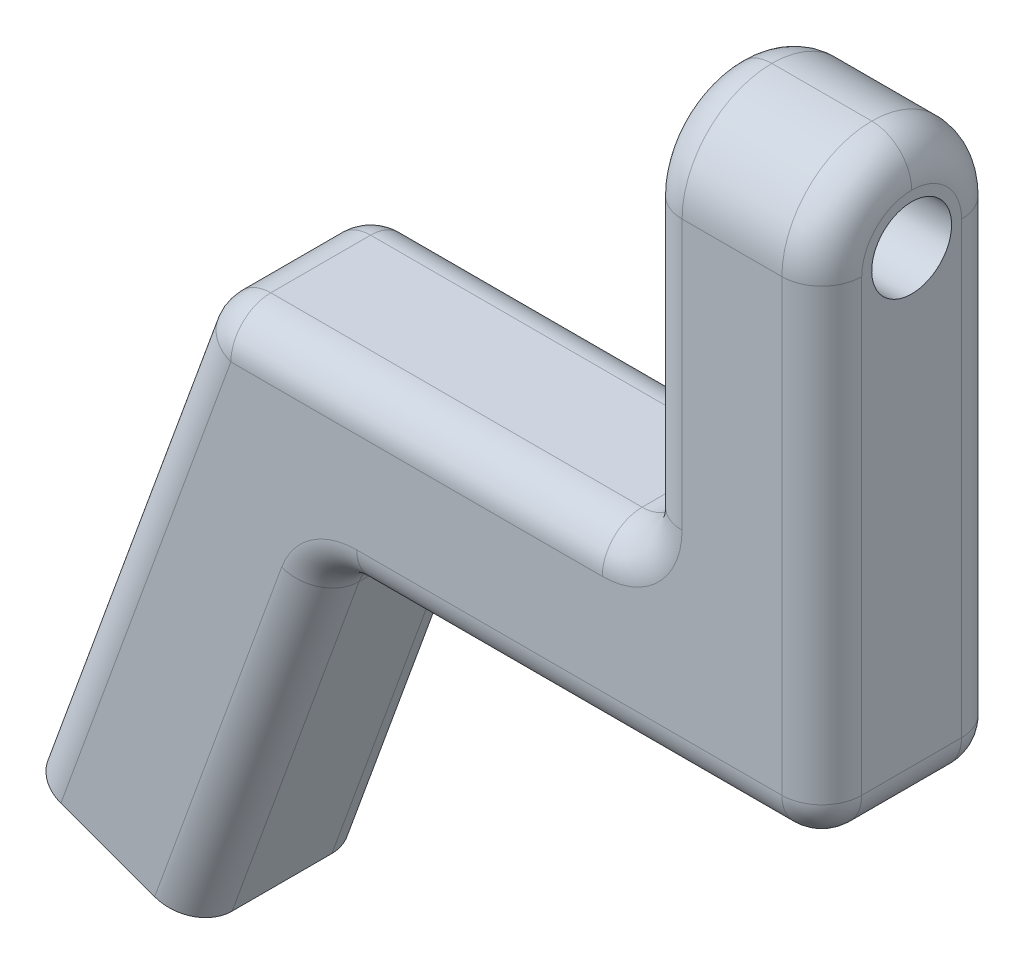
SolidWorks part; units mm, degrees
ref_plane "Ön Düzlem" through (0, 0, 0) normal (0, 0, 1) x (1, 0, 0)
ref_plane "Üst Düzlem" through (0, 0, 0) normal (0, 1, 0) x (1, 0, 0)
ref_plane "Sağ Düzlem" through (0, 0, 0) normal (1, 0, 0) x (0, 0, -1)
sketch "Çizim1" plane through (0, 0, 0) normal (0, 0, 1) x (1, 0, 0)
  line L0 (0, 0) -> (8.9958, 24.7157)
  line L1 (8.9958, 24.7157) -> (30.9958, 24.7157)
  line L2 (30.9958, 24.7157) -> (30.9958, 44.7157)
  line L3 (30.9958, 44.7157) -> (39.9958, 44.7157)
  line L4 (39.9958, 44.7157) -> (39.9958, 15.7157)
  line L5 (39.9958, 15.7157) -> (15.2976, 15.7157)
  line L6 (15.2976, 15.7157) -> (8.4572, -3.0782)
  line L7 (8.4572, -3.0782) -> (0, 0)
  line L9 (0, 0) -> (0, 42.7901) construction
  dimension "D1" = 9
  dimension "D2" = 20
  dimension "D3" = 9
  dimension "D4" = 9
  dimension "D5" = 20
  dimension "D6" = 22
  dimension "D7" = 20
extrude "Yükseklik-Ekstrüzyon1" add sketch "Çizim1" along normal blind 9
fillet "Radyus1" radius 4.5 2 edges at (35.4958, 44.7157, 0) (35.4958, 44.7157, 9)
sketch "Çizim2" plane through (39.9958, 0, 0) normal (1, 0, 0) x (0, 0, -1)
  circle A0 centre (-4.5, 40.2157) radius 2
  dimension "D1" = 4
extrude "Kes-Ekstrüzyon1" cut sketch "Çizim2" against normal blind 9
sketch "Çizim3" plane through (0, 0, 0) normal (-0.342, -0.9397, 0) x (0.9397, -0.342, 0)
  line L0 (0, 9) -> (0, 0) construction
  line L1 (0, 0) -> (9, 0) construction
  circle A0 centre (4.5, 4.5) radius 2.575
  dimension "D1" = 5.15
  dimension "D2" = 4.5
  dimension "D3" = 4.5
extrude "Kes-Ekstrüzyon2" cut sketch "Çizim3" against normal blind 15
fillet "Radyus2" radius 2 20 edges at (30.9958, 32.4657, 0) (30.9958, 43.3977, 1.318) (30.9958, 43.3977, 7.682) (39.9958, 27.9657, 0) (39.9958, 43.3977, 1.318) (39.9958, 43.3977, 7.682) (39.9958, 15.7157, 4.5) (15.2976, 15.7157, 4.5) (30.9958, 24.7157, 4.5) (8.9958, 24.7157, 4.5) (19.9958, 24.7157, 9) (19.9958, 24.7157, 0) (4.4979, 12.3578, 0) (4.4979, 12.3578, 9) (30.9958, 32.4657, 9) (11.8774, 6.3187, 0) (27.6467, 15.7157, 0) (39.9958, 27.9657, 9) (27.6467, 15.7157, 9) (11.8774, 6.3187, 9)
